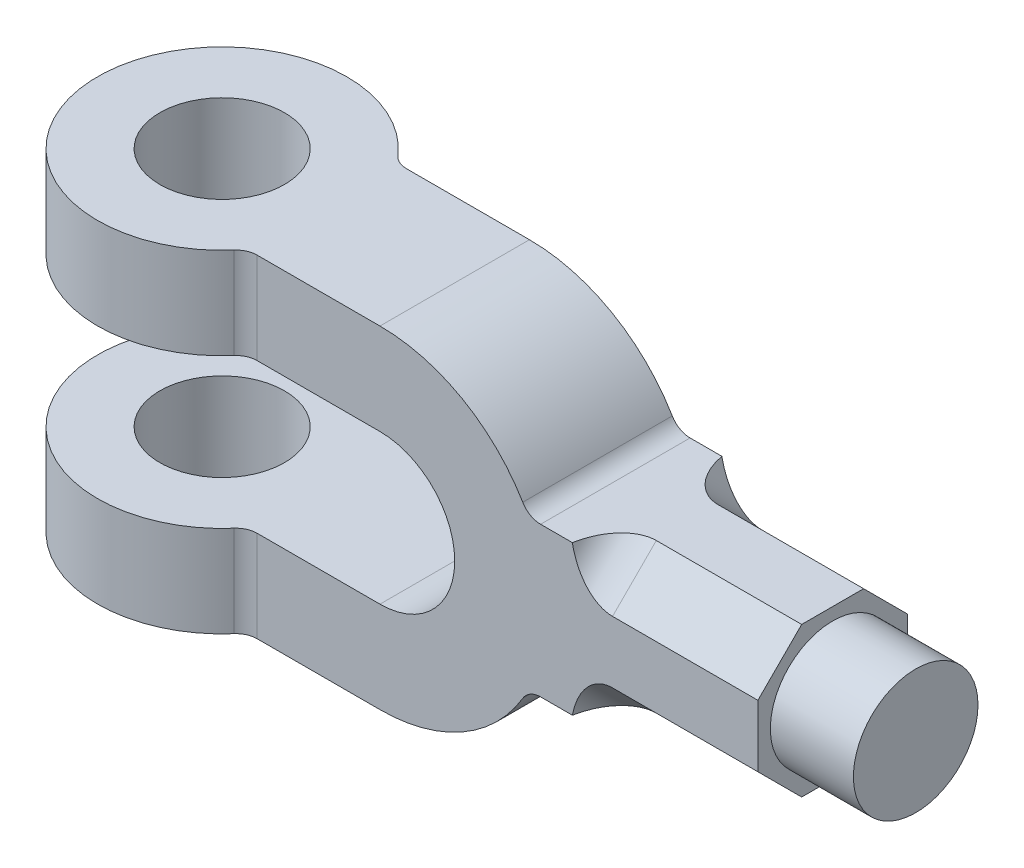
SolidWorks part; units mm, degrees
ref_plane "Front Plane" through (0, 0, 0) normal (0, 0, 1) x (1, 0, 0)
ref_plane "Top Plane" through (0, 0, 0) normal (0, 1, 0) x (1, 0, 0)
ref_plane "Right Plane" through (0, 0, 0) normal (1, 0, 0) x (0, 0, -1)
sketch "Croquis2" plane through (0, 0, 0) normal (0, 1, 0) x (1, 0, 0)
  line L0 (0, 0) -> (4, 0) construction
  line L1 (147, -42.0547) -> (38, -42.0547) construction
  line L3 (24, -18) -> (56, -18)
  line L5 (24, 18) -> (56, 18)
  line L6 (56, -18) -> (56, 18)
  line L7 (30, 0) -> (56, 18) construction
  line L8 (30, 0) -> (56, -18) construction
  line L9 (30, 0) -> (147, 0) construction
  arc A0 (24, 18) -> (24, -18) centre (0, 0) ccw
  circle A1 centre (0, 0) radius 15
  point P7 (30, 0)
  point P13 (30, 0)
  dimension "D1" = 60
  dimension "D2" = 30
  dimension "D3" = 147
  dimension "D4" = 109
  dimension "D5" = 36
  dimension "D6" = 18
extrude "Saliente-Extruir1" add sketch "Croquis2" along normal mid plane 80
sketch "Croquis3" plane through (0, 0, 0) normal (0, 0, 1) x (1, 0, 0)
  line L0 (24, 40) -> (-30, 40) construction
  line L1 (-34.157, 18) -> (65.3173, 18)
  line L2 (-34.157, 18) -> (-34.157, -18)
  line L3 (-34.157, -18) -> (65.3173, -18)
  line L4 (65.3173, 18) -> (65.3173, -18)
  dimension "D1" = 22
  dimension "D2" = 36
extrude "Cortar-Extruir1" cut sketch "Croquis3" against normal mid plane 80
sketch "Croquis5" plane through (0, 0, 18) normal (0, 0, 1) x (1, 0, 0)
  line L0 (56, -18) -> (56, -40) construction
  line L1 (0, 0) -> (74, 0) construction
  line L2 (147, 62.72) -> (38, 62.72) construction
  line L3 (96, 0) -> (147, 0) construction
  line L4 (91.7211, 18) -> (102, 18)
  line L6 (91.7211, -18) -> (102, -18)
  line L7 (102, 18) -> (102, -18)
  line L8 (56, 40) -> (56, 18)
  line L9 (56, -40) -> (56, -18)
  arc A0 (56, 18) -> (56, -18) centre (56, 0) cw
  arc A1 (56, 40) -> (91.7211, 18) centre (56, 0) cw
  arc A2 (91.7211, -18) -> (56, -40) centre (56, 0) cw
  point P16 (67.4221, 0)
  point P18 (67.4221, 0)
  dimension "D1" = 147
  dimension "D2" = 109
  dimension "D3" = 45
  dimension "D4" = 18
  dimension "D5" = 18
extrude "Saliente-Extruir2" add sketch "Croquis5" against normal blind 36
sketch "Croquis7" plane through (102, 0, 0) normal (1, 0, 0) x (0, 0, -1)
  line L10 (18, 18) -> (-18, 18) construction
  line L11 (-7.4558, 18) -> (-18, 7.4558)
  line L12 (-18, 7.4558) -> (-18, -7.4558)
  line L13 (-18, -7.4558) -> (-7.4558, -18)
  line L14 (-7.4558, -18) -> (7.4558, -18)
  line L15 (7.4558, -18) -> (18, -7.4558)
  line L16 (18, -7.4558) -> (18, 7.4558)
  line L17 (18, 7.4558) -> (7.4558, 18)
  line L18 (7.4558, 18) -> (-7.4558, 18)
  circle A0 centre (0, 0) radius 18 construction
  dimension "D1" = 36
extrude "Saliente-Extruir3" add sketch "Croquis7" along normal blind 45
sketch "Croquis8" plane through (147, 0, 0) normal (1, 0, 0) x (0, 0, -1)
  circle A0 centre (0, 0) radius 15
  dimension "D1" = 30
extrude "Saliente-Extruir4" add sketch "Croquis8" along normal blind 20
fillet "Redondeo1" radius 10 4 edges at (102, 12.7279, 12.7279) (102, 12.7279, -12.7279) (102, -12.7279, -12.7279) (102, -12.7279, 12.7279)
fillet "Redondeo2" radius 5 2 edges at (91.7211, 18, 0) (91.7211, -18, 0)
fillet "Redondeo3" radius 5 4 edges at (24, -29, -18) (24, -29, 18) (24, 29, -18) (24, 29, 18)
